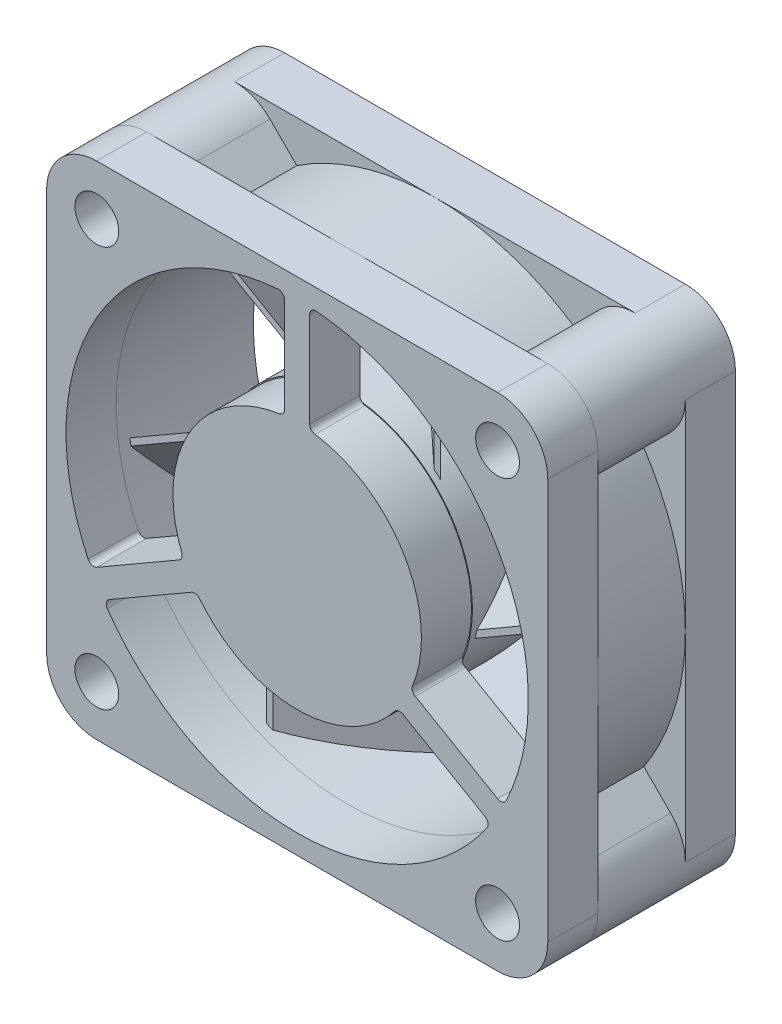
SolidWorks part; units mm, degrees
note: '?' marks a value the reader was unsure of.
ref_plane "Front Plane" through (0, 0, 0) normal (0, 0, 1) x (1, 0, 0)
ref_plane "Top Plane" through (0, 0, 0) normal (0, 1, 0) x (1, 0, 0)
ref_plane "Right Plane" through (0, 0, 0) normal (1, 0, 0) x (0, 0, -1)
sketch "Sketch1" plane through (0, 0, 0) normal (0, 0, 1) x (1, 0, 0)
  line L0 (-16.0125, -20.0125) -> (16.0125, -20.0125)
  line L1 (-20.0125, -16.0125) -> (-20.0125, 16.0125)
  line L2 (20.0125, -16.0125) -> (20.0125, 16.0125)
  line L3 (-16.0125, 20.0125) -> (16.0125, 20.0125)
  line L4 (-20.0125, -20.0125) -> (20.0125, 20.0125) construction
  line L5 (20.0125, -20.0125) -> (-20.0125, 20.0125) construction
  line L6 (0, 0) -> (0, 21.9829) construction
  line L7 (0, 0) -> (19.0377, -10.9914) construction
  line L8 (0, 0) -> (-19.0377, -10.9914) construction
  line L9 (1, 9.8737) -> (1, 18.432)
  line L10 (9.0509, -4.0708) -> (16.4626, -8.35)
  line L11 (-1, 9.8737) -> (-1, 18.432)
  line L12 (8.0509, -5.8029) -> (15.4626, -10.082)
  line L13 (-8.0509, -5.8029) -> (-15.4626, -10.082)
  line L14 (-9.0509, -4.0708) -> (-16.4626, -8.35)
  circle A0 centre (-16, 16) radius 1.75
  circle A1 centre (16, 16) radius 1.75
  circle A2 centre (16, -16) radius 1.75
  circle A3 centre (-16, -16) radius 1.75
  arc A4 (-1, 18.432) -> (-16.4626, -8.35) centre (0, 0) ccw
  arc A5 (-1, 9.8737) -> (8.0509, -5.8029) centre (0, 0) ccw
  arc A6 (16.4626, -8.35) -> (1, 18.432) centre (0, 0) ccw
  arc A7 (9.0509, -4.0708) -> (1, 9.8737) centre (0, 0) ccw
  arc A8 (-15.4626, -10.082) -> (15.4626, -10.082) centre (0, 0) ccw
  arc A9 (16.0125, -20.0125) -> (20.0125, -16.0125) centre (16.0125, -16.0125) ccw
  arc A10 (-20.0125, -16.0125) -> (-16.0125, -20.0125) centre (-16.0125, -16.0125) ccw
  arc A11 (-20.0125, 16.0125) -> (-16.0125, 20.0125) centre (-16.0125, 16.0125) cw
  arc A12 (20.0125, 16.0125) -> (16.0125, 20.0125) centre (16.0125, 16.0125) ccw
  point P1 (0, 0)
  point P17 (0, 0)
  point P23 (0, 0)
  point P32 (0, 0)
  point P37 (0, 0)
  dimension "D1" = 4
  dimension "D2" = 3
  dimension "D4" = 4
  dimension "D3" = 3
extrude "Boss-Extrude1" add sketch "Sketch1" along normal blind 4
sketch "Sketch2" plane through (0, 0, 0) normal (0, 0, -1) x (-1, 0, 0)
  line L1 (-18.8284, 13.1716) -> (-16.6848, 11.028)
  line L2 (-13.1716, 18.8284) -> (-11.028, 16.6848)
  line L3 (18.8284, 13.1716) -> (16.6848, 11.028)
  line L4 (13.1716, 18.8284) -> (11.028, 16.6848)
  line L5 (13.1716, -18.8284) -> (11.028, -16.6848)
  line L6 (18.8284, -13.1716) -> (16.6848, -11.028)
  line L7 (-18.8284, -13.1716) -> (-16.6848, -11.028)
  line L8 (-13.1716, -18.8284) -> (-11.028, -16.6848)
  arc A0 (-16.6848, 11.028) -> (-16.6848, -11.028) centre (0, 0) ccw
  circle A1 centre (0, 0) radius 18.5
  arc A3 (-13.1716, 18.8284) -> (-18.8284, 13.1716) centre (-16, 16) ccw
  arc A4 (18.8284, 13.1716) -> (13.1716, 18.8284) centre (16, 16) ccw
  arc A5 (13.1716, -18.8284) -> (18.8284, -13.1716) centre (16, -16) ccw
  arc A6 (-18.8284, -13.1716) -> (-13.1716, -18.8284) centre (-16, -16) ccw
  arc A7 (11.028, 16.6848) -> (-11.028, 16.6848) centre (0, 0) ccw
  arc A8 (16.6848, -11.028) -> (16.6848, 11.028) centre (0, 0) ccw
  arc A9 (-11.028, -16.6848) -> (11.028, -16.6848) centre (0, 0) ccw
  circle A10 centre (-16, 16) radius 1.75
  circle A11 centre (16, 16) radius 1.75
  circle A12 centre (16, -16) radius 1.75
  circle A13 centre (-16, -16) radius 1.75
  point P29 (0, 0)
  dimension "D1" = 4
extrude "Boss-Extrude2" add sketch "Sketch2" along normal blind 7
ref_plane "Plane2" through (0, 0, -7) normal (0, 0, 1) x (1, 0, 0)
sketch "Sketch3" plane through (0, 0, -7) normal (0, 0, 1) x (1, 0, 0)
  line L1 (-16, 20) -> (16, 20)
  line L2 (-20, 16) -> (-20, -16)
  line L3 (-16, -20) -> (16, -20)
  line L4 (20, 16) -> (20, -16)
  circle A0 centre (0, 0) radius 18.5
  circle A1 centre (-16, 16) radius 1.75
  circle A2 centre (16, 16) radius 1.75
  circle A3 centre (16, -16) radius 1.7065
  circle A4 centre (-16, -16) radius 1.75
  arc A5 (16, -20) -> (20, -16) centre (16, -16) ccw
  arc A6 (-20, -16) -> (-16, -20) centre (-16, -16) ccw
  arc A7 (16, 20) -> (20, 16) centre (16, 16) cw
  arc A8 (-16, 20) -> (-20, 16) centre (-16, 16) ccw
  dimension "D1" = 4
extrude "Boss-Extrude3" add sketch "Sketch3" against normal blind 4
sketch "Sketch4" plane through (0, 0, 0) normal (0, 0, -1) x (-1, 0, 0)
  circle A0 centre (0, 0) radius 2
extrude "Boss-Extrude4" add sketch "Sketch4" along normal blind 0.5
sketch "Sketch5" plane through (0, 0, 0) normal (0, 0, -1) x (-1, 0, 0)
  circle A0 centre (0, 0) radius 10
extrude "Boss-Extrude5" add sketch "Sketch5" along normal blind 11
fillet "Fillet1" radius 0.5 13 edges at (-10, 0, -11) (1, 18.432, 2) (-1, 18.432, 2) (-16.4626, -8.35, 2) (-15.4626, -10.082, 2) (15.4626, -10.082, 2) (16.4626, -8.35, 2) (9.0509, -4.0708, 2) (1, 9.8737, 2) (-1, 9.8737, 2) (-9.0509, -4.0708, 2) (8.0509, -5.8029, 2) (-8.0509, -5.8029, 2)
sketch "Sketch6" plane through (0, 0, 0) normal (0, 1, 0) x (1, 0, 0)
  line L1 (6.43, 0.5) -> (-4.8, 10.5)
  line L2 (-4.3268, 10.5) -> (6.93, 0.5)
  line L4 (-4.8, 10.5) -> (-4.3268, 10.5)
  line L7 (6.93, 0.5) -> (6.43, 0.5)
  dimension "D3" = 0.5
extrude "Boss-Extrude6" add sketch "Sketch6" along normal offset from surface (16.6125 mm away) 0.5
ref_axis "Axis1" through (0, 0, -11.75) along (0, 0, 1)?
pattern_circular "CirPattern1" count 6 over 360 about axis through (0, 0, 0) along (0, 0, 1) of "Boss-Extrude6"
